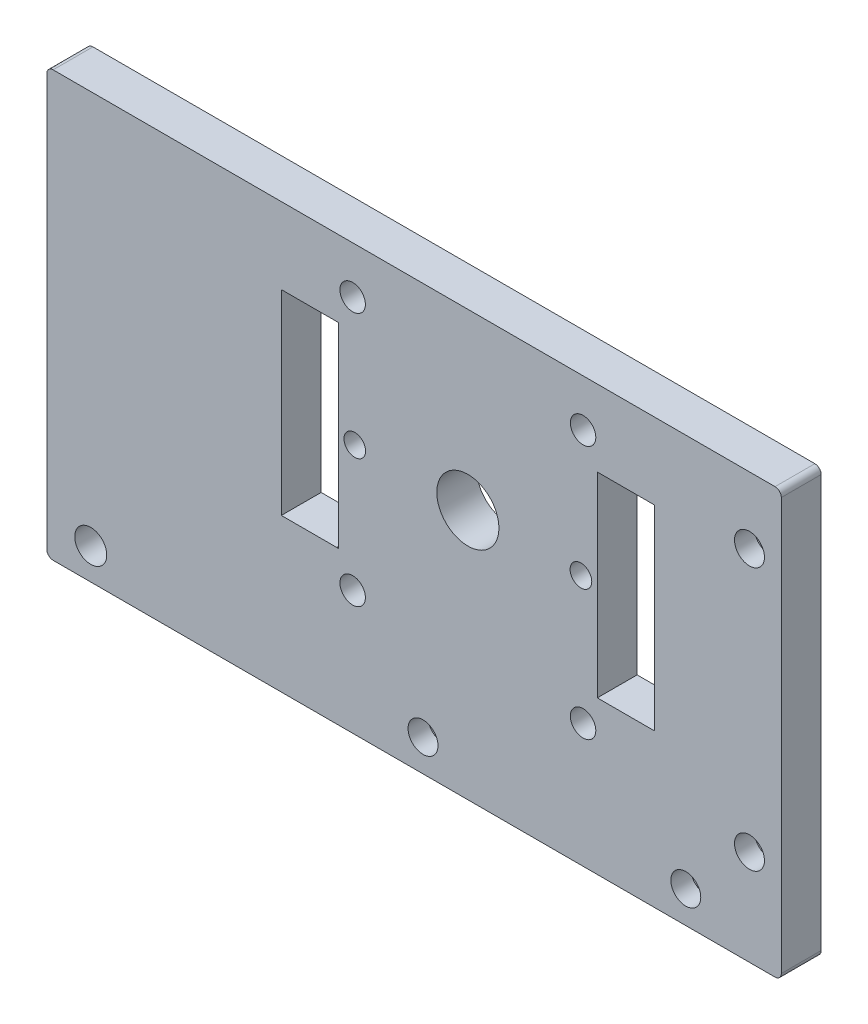
SolidWorks part; units mm, degrees
ref_plane "Front Plane" through (0, 0, 0) normal (0, 0, 1) x (1, 0, 0)
ref_plane "Top Plane" through (0, 0, 0) normal (0, 1, 0) x (1, 0, 0)
ref_plane "Right Plane" through (0, 0, 0) normal (1, 0, 0) x (0, 0, -1)
sketch "Brace Ref" plane through (0, 0, 0) normal (0, 0, 1) x (1, 0, 0)
  line B0 (-76.454, 5.6642) -> (-76.454, 10.0838)
  line B1 (-75.8588, 11.5206) -> (-73.7506, 13.6288)
  line B2 (-72.3138, 14.224) -> (-61.0148, 14.224)
  line B3 (-61.0148, 14.224) -> (-38.7641, 15.001)
  line B4 (-75.8588, 4.2274) -> (-73.7506, 2.1192)
  line B5 (-72.3138, 1.524) -> (-61.5696, 1.524)
  line B6 (-57.8366, 0) -> (-21.4114, 0)
  line B7 (-17.6784, 1.524) -> (-5.6642, 1.524)
  line B8 (-4.2274, 2.1192) -> (-2.1192, 4.2274)
  line B9 (-1.524, 5.6642) -> (-1.524, 17.6784)
  line B10 (0, 21.4114) -> (0, 57.8366)
  line B11 (-1.524, 61.5696) -> (-1.524, 72.3138)
  line B12 (-2.1192, 73.7506) -> (-4.2274, 75.8588)
  line B13 (-5.6642, 76.454) -> (-10.0838, 76.454)
  line B14 (-11.5206, 75.8588) -> (-13.6288, 73.7506)
  line B15 (-14.224, 72.3138) -> (-14.224, 61.0148)
  line B16 (-14.224, 61.0148) -> (-15.001, 38.7641)
  line B17 (-76.454, 0) -> (-76.454, 76.454) construction
  line B18 (-76.454, 0) -> (0, 0) construction
  line B19 (0, 0) -> (0, 76.454) construction
  line B20 (-76.454, 76.454) -> (0, 76.454) construction
  arc B21 (-76.454, 10.0838) -> (-75.8588, 11.5206) centre (-74.422, 10.0838) cw
  arc B22 (-73.7506, 13.6288) -> (-72.3138, 14.224) centre (-72.3138, 12.192) cw
  arc B23 (-38.7641, 15.001) -> (-27.0035, 18.4638) centre (-39.624, 39.624) ccw
  arc B24 (-27.0035, 18.4638) -> (-25.4333, 20.7849) centre (-28.6949, 21.2997) ccw
  arc B25 (-25.4333, 20.7849) -> (-20.7849, 25.4333) centre (-19.9136, 19.9136) cw
  arc B26 (-76.454, 5.6642) -> (-75.8588, 4.2274) centre (-74.422, 5.6642) ccw
  arc B27 (-73.7506, 2.1192) -> (-72.3138, 1.524) centre (-72.3138, 3.556) ccw
  arc B28 (-61.5696, 1.524) -> (-59.2587, 0.5806) centre (-61.5696, -1.778) cw
  arc B29 (-59.2587, 0.5806) -> (-57.8366, 0) centre (-57.8366, 2.032) ccw
  arc B30 (-21.4114, 0) -> (-19.9893, 0.5806) centre (-21.4114, 2.032) ccw
  arc B31 (-19.9893, 0.5806) -> (-17.6784, 1.524) centre (-17.6784, -1.778) cw
  arc B32 (-5.6642, 1.524) -> (-4.2274, 2.1192) centre (-5.6642, 3.556) ccw
  arc B33 (-2.1192, 4.2274) -> (-1.524, 5.6642) centre (-3.556, 5.6642) ccw
  arc B34 (-1.524, 17.6784) -> (-0.5806, 19.9893) centre (1.778, 17.6784) cw
  arc B35 (-0.5806, 19.9893) -> (0, 21.4114) centre (-2.032, 21.4114) ccw
  arc B36 (0, 57.8366) -> (-0.5806, 59.2587) centre (-2.032, 57.8366) ccw
  arc B37 (-0.5806, 59.2587) -> (-1.524, 61.5696) centre (1.778, 61.5696) cw
  arc B38 (-1.524, 72.3138) -> (-2.1192, 73.7506) centre (-3.556, 72.3138) ccw
  arc B39 (-4.2274, 75.8588) -> (-5.6642, 76.454) centre (-5.6642, 74.422) ccw
  arc B40 (-10.0838, 76.454) -> (-11.5206, 75.8588) centre (-10.0838, 74.422) ccw
  arc B41 (-13.6288, 73.7506) -> (-14.224, 72.3138) centre (-12.192, 72.3138) ccw
  arc B42 (-15.001, 38.7641) -> (-18.4638, 27.0035) centre (-39.624, 39.624) cw
  arc B43 (-18.4638, 27.0035) -> (-20.7849, 25.4333) centre (-21.2997, 28.6949) cw
  circle B44 centre (-70.104, 7.874) radius 4.3561
  circle B45 centre (-19.9136, 19.9136) radius 2.3813
  circle B46 centre (-7.874, 70.104) radius 4.3561
sketch_block_instance "Block1-1"
sketch_block "Block1" parameters "D1"=31.75, "D2"=30.48, "D3"=30.48, "D4"=31.75, "D5"=19.7104, "D6"=19.7104
sketch "Sketch5" plane through (0, 0, 0) normal (0, 0, 1) x (1, 0, 0)
  line L0 (-52.794, 47.747) -> (-52.794, 42.794) construction
  line L1 (-94.544, 70.544) -> (-2.794, 70.544)
  line L2 (-94.544, 70.544) -> (-94.544, 2.794)
  line L3 (-94.544, 2.794) -> (-2.794, 2.794)
  line L4 (-2.794, 70.544) -> (-2.794, 2.794)
  line L6 (-82.794, 58.794) -> (-22.794, 58.794) construction
  line L7 (-82.794, 58.794) -> (-82.794, 26.794) construction
  line L8 (-70.828, 42.794) -> (-52.794, 42.794) construction
  line L9 (-84.544, 60.544) -> (-21.044, 60.544) construction
  line L10 (-52.794, 42.794) -> (-34.76, 42.794) construction
  line L11 (-84.544, 60.544) -> (-84.544, 25.044) construction
  line L12 (-84.544, 25.044) -> (-21.044, 25.044) construction
  line L13 (-21.044, 60.544) -> (-21.044, 25.044) construction
  line L14 (-89.544, 65.544) -> (-16.044, 65.544) construction
  line L15 (-82.794, 26.794) -> (-22.794, 26.794) construction
  line L16 (-22.794, 58.794) -> (-22.794, 26.794) construction
  line L17 (-82.544, 58.394) -> (-73.694, 58.394)
  line L18 (-89.544, 65.544) -> (-89.544, 20.044) construction
  line L19 (-89.544, 20.044) -> (-16.044, 20.044) construction
  line L20 (-16.044, 65.544) -> (-16.044, 20.044) construction
  line L21 (-82.544, 58.394) -> (-82.544, 27.194)
  line L22 (-82.544, 27.194) -> (-73.694, 27.194)
  line L23 (-73.694, 58.394) -> (-73.694, 27.194)
  line L24 (-31.894, 58.394) -> (-23.044, 58.394)
  line L25 (-31.894, 58.394) -> (-31.894, 27.194)
  line L26 (-31.894, 27.194) -> (-23.044, 27.194)
  line L27 (-23.044, 58.394) -> (-23.044, 27.194)
  line L28 (-82.544, 58.394) -> (-82.794, 58.394) construction
  line L30 (-23.044, 58.394) -> (-22.794, 58.394) construction
  circle A7 centre (-52.794, 42.794) radius 4.953
  circle A10 centre (-19.9136, 19.9136) radius 3.683
  circle A14 centre (-59.944, 7.874) radius 1.5875
  circle A15 centre (-18.034, 7.874) radius 1.5875
  circle A16 centre (-7.874, 18.034) radius 1.5875
  circle A17 centre (-7.874, 59.944) radius 1.5875
  circle A18 centre (-19.9136, 19.9136) radius 2.3813 construction
  circle A19 centre (-70.828, 42.794) radius 1.6666 construction
  circle A21 centre (-34.76, 42.794) radius 1.6666 construction
  circle A22 centre (-42.794, 37.794) radius 0.5 construction
  circle A23 centre (-59.944, 7.874) radius 2.3876
  circle A24 centre (-18.034, 7.874) radius 2.3876
  circle A25 centre (-7.874, 59.944) radius 2.3876
  circle A26 centre (-7.874, 18.034) radius 2.3876
  circle A32 centre (-52.794, 42.794) radius 4.953
  circle A35 centre (-52.794, 42.794) radius 4.953
  circle A38 centre (-52.794, 42.794) radius 4.953
  point P6 (-52.794, 58.794)
  point P17 (-22.794, 42.794)
  point P25 (-52.794, 65.544)
  point P26 (-16.044, 42.794)
  point P39 (-73.694, 42.794)
  point P116 (-52.794, 42.794)
  dimension "D8" = 7.366
  dimension "D9" = 3.175
  dimension "D10" = 4.7752
  dimension "D2" = 9.906
  dimension "D22" = 3.3332
  dimension "D30" = 1
  dimension "D6" = 17.1196
  dimension "D7" = 17.1196
  dimension "D12" = 41.91
  dimension "D13" = 5.08
  dimension "D14" = 5.08
  dimension "D15" = 41.91
  dimension "D16" = 15.24
  dimension "D17" = 15.24
  dimension "D11" = 18.034
  dimension "D3" = 63.5
  dimension "D5" = 5
  dimension "D18" = 5
  dimension "D19" = 5
  dimension "D20" = 5
  dimension "D21" = 35.5
  dimension "D23" = 60
  dimension "D24" = 32
  dimension "D25" = 31.2
  dimension "D26" = 0.25
  dimension "D27" = 8.85
  dimension "D28" = 40
  dimension "D29" = 35
  dimension "D32" = 10
  dimension "D33" = 5
  dimension "D34" = 5
  dimension "D31" = 5
extrude "Boss-Extrude1" add sketch "Sketch5" along normal blind 6.35 contours L4 L1 L2 L3 A26 A25 A24 A23 A10 A7 L17 L23 L22 L21 L24 L27 L26 L25 | A25 A17 | A10 | A26 A16 | A24 A15 | A23 A14 region at (-48.7489, 36.2684, 0) region at (-19.9136, 19.9136, 0) region at (-62.2641, 7.874, 0) region at (-20.3541, 7.874, 0) region at (-10.1941, 59.944, 0) region at (-10.1941, 18.034, 0)
hole_wizard "#8-32 Tapped Hole1" positions "3DSketch1" profile "Sketch6" tap size "#8-32" standard "ANSI Inch" end condition through all
sketch3d "3DSketch1"
  point P0 (-70.828, 42.794, 6.35)
  point P2 (-34.76, 42.794, 6.35)
sketch "Sketch6" plane through (-70.828, 42.794, 6.35) normal (1, 0, 0) x (0, -1, 0)
  line L0 (0, 0) -> (0, 6.35)
  line L1 (0, 6.35) -> (1.7272, 6.35)
  line L2 (1.7272, 6.35) -> (1.7272, 0)
  line L5 (1.7272, 0) -> (0, 0)
  line L11 (0, -6.35) -> (0, 107.95) construction
  dimension "Thru Tap Drill Dia." = 3.4544
  dimension "Thru Tap Drill Depth" = 6.35
cosmetic thread "Hole Thread1" parameters "D2"=4.1656
cosmetic thread "Hole Thread2" parameters "D2"=4.1656
extrude "Cut-Extrude2" cut sketch "Sketch5<3>" against normal blind 3.175 from surface contours A24 A15 | A26 A16 | A23 A14 | A25 A17 region at (-62.2641, 7.874, 0) region at (-20.3541, 7.874, 0) region at (-10.1941, 59.944, 0) region at (-10.1941, 18.034, 0) starting at face at (-69.1008, 42.794, 6.35)
sketch "Sketch5<3>" plane through (0, 0, 0) normal (0, 0, 1) x (1, 0, 0) same geometry as "Sketch5"
fillet "Fillet1" [suppressed] radius 6.35
sketch "Sketch8" plane through (0, 0, 0) normal (0, 0, 1) x (1, 0, 0)
  line L1 (-94.544, 2.794) -> (-119.944, 2.794)
  line L2 (-94.544, 2.794) -> (-94.544, 70.544)
  line L3 (-94.544, 70.544) -> (-119.944, 70.544)
  line L4 (-119.944, 2.794) -> (-119.944, 70.544)
  circle A0 centre (-112.944, 7.794) radius 1
  dimension "D2" = 2
  dimension "D1" = 25.4
  dimension "D3" = 5
  dimension "D4" = 7
extrude "Boss-Extrude2" add sketch "Sketch8" along normal up to surface (6.35 mm away) up to face at (-5.4864, 59.944, 6.35)
hole_wizard "1/4-20 Tapped Hole2" positions "3DSketch3" profile "Sketch10" tap size "1/4-20" standard "ANSI Inch" end condition through all
sketch3d "3DSketch3"
  line L0 (-112.944, 7.794, 6.35) -> (-112.944, 7.794, 0) construction
  point P0 (-112.944, 7.794, 6.35)
sketch "Sketch10" plane through (-112.944, 7.794, 6.35) normal (1, 0, 0) x (0, -1, 0)
  line L0 (0, 0) -> (0, 6.35)
  line L1 (0, 6.35) -> (2.5527, 6.35)
  line L2 (2.5527, 6.35) -> (2.5527, 0)
  line L5 (2.5527, 0) -> (0, 0)
  line L11 (0, -6.35) -> (0, 107.95) construction
  dimension "Thru Tap Drill Dia." = 5.1054
  dimension "Thru Tap Drill Depth" = 6.35
cosmetic thread "Hole Thread3" parameters "D2"=6.35
sketch "Sketch11" plane through (0, 0, 6.35) normal (0, 0, 1) x (1, 0, 0)
  line L0 (-2.794, 70.544) -> (-2.794, 2.794) construction
  line L1 (-71.169, 63.044) -> (-34.419, 63.044) construction
  line L2 (-71.169, 63.044) -> (-71.169, 22.544) construction
  line L3 (-71.169, 22.544) -> (-34.419, 22.544) construction
  line L4 (-34.419, 63.044) -> (-34.419, 22.544) construction
  line L5 (-119.944, 2.794) -> (-2.794, 2.794) construction
  circle A0 centre (-71.169, 63.044) radius 2.032
  circle A1 centre (-34.419, 63.044) radius 2.032
  circle A2 centre (-34.419, 22.544) radius 2.032
  circle A3 centre (-71.169, 22.544) radius 2.032
  dimension "D5" = 4.064
  dimension "D1" = 31.625
  dimension "D2" = 19.75
  dimension "D3" = 36.75
  dimension "D4" = 40.5
extrude "Cut-Extrude3" cut sketch "Sketch11" against normal through all both and the other way through all
sketch "Sketch12" plane through (0, 0, 6.35) normal (0, 0, 1) x (1, 0, 0)
  line L0 (-31.894, 27.194) -> (-23.044, 27.194) construction
  line L1 (-31.894, 58.394) -> (-32.144, 58.394)
  line L2 (-31.894, 58.394) -> (-31.894, 27.194)
  line L3 (-31.894, 27.194) -> (-32.144, 27.194)
  line L4 (-32.144, 58.394) -> (-32.144, 27.194)
  line L5 (-73.694, 58.394) -> (-73.444, 58.394)
  line L6 (-73.694, 58.394) -> (-73.694, 27.1714)
  line L7 (-73.694, 27.1714) -> (-73.444, 27.1714)
  line L8 (-73.444, 58.394) -> (-73.444, 27.1714)
  dimension "D1" = 0.25
extrude "Cut-Extrude4" cut sketch "Sketch12" against normal through all both and the other way through all
fillet "Fillet2" radius 1 4 edges at (-119.944, 70.544, 3.175) (-119.944, 2.794, 3.175) (-2.794, 70.544, 3.175) (-2.794, 2.794, 3.175)
equation "\"D18@Sketch5\"=\"D5@Sketch5\""
equation "\"D19@Sketch5\"=\"D18@Sketch5\""
equation "\"D20@Sketch5\"=\"D5@Sketch5\""
equation "\"D2@Sketch11\"=21.55mm-1.8"
equation "\"D1@Sketch11\"=28.425mm+3.2"
